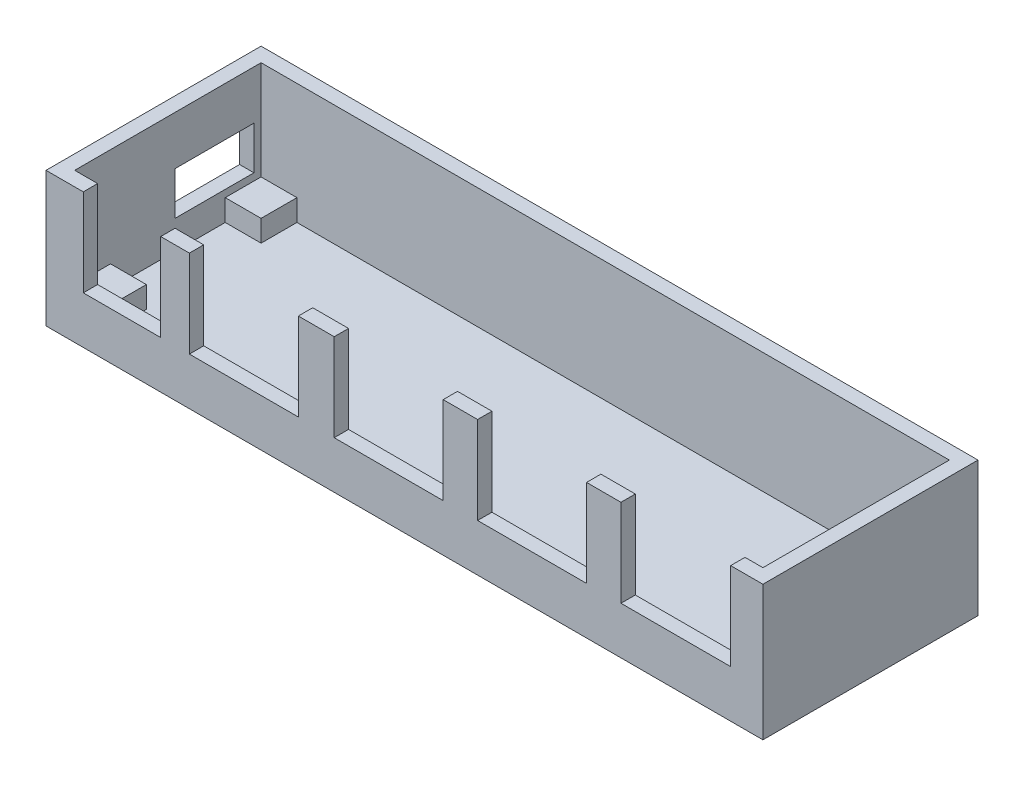
SolidWorks part; units mm, degrees
ref_plane "Front Plane" through (0, 0, 0) normal (0, 0, 1) x (1, 0, 0)
ref_plane "Top Plane" through (0, 0, 0) normal (0, 1, 0) x (1, 0, 0)
ref_plane "Right Plane" through (0, 0, 0) normal (1, 0, 0) x (0, 0, -1)
sketch "Sketch1" plane through (0, 0, 0) normal (0, 1, 0) x (1, 0, 0)
  line L0 (-87.4712, -27.9663) -> (8.5288, -27.9663)
  line L1 (-89.4712, -55.9663) -> (10.5288, -55.9663)
  line L2 (-89.4712, -55.9663) -> (-89.4712, -25.9663)
  line L3 (-89.4712, -25.9663) -> (10.5288, -25.9663)
  line L4 (10.5288, -55.9663) -> (10.5288, -25.9663)
  line L5 (8.5288, -53.9663) -> (8.5288, -27.9663)
  line L6 (-87.4712, -53.9663) -> (8.5288, -53.9663)
  line L7 (-87.4712, -53.9663) -> (-87.4712, -27.9663)
  line L8 (6.0288, -53.9663) -> (6.0288, -55.9663)
  line L9 (-9.2712, -53.9663) -> (-9.2712, -55.9663)
  line L10 (-14.0712, -53.9663) -> (-14.0712, -55.9663)
  line L11 (-34.0712, -53.9663) -> (-34.0712, -55.9663)
  line L12 (-54.2712, -53.9663) -> (-54.2712, -55.9663)
  line L13 (-29.2712, -53.9663) -> (-29.2712, -55.9663)
  line L14 (-49.2712, -53.9663) -> (-49.2712, -55.9663)
  line L15 (-69.4712, -53.9663) -> (-69.4712, -55.9663)
  line L16 (-73.4712, -53.9663) -> (-73.4712, -55.9663)
  line L17 (-84.2712, -53.9663) -> (-84.2712, -55.9663)
  line L18 (-39.9712, -12.3854) -> (-39.9712, -67.4293) construction
  line L20 (8.5288, -27.9663) -> (8.5288, -32.9663)
  line L24 (-87.4712, -27.9663) -> (-87.4712, -32.9663)
  line L25 (-91.4683, -40.9663) -> (18.0521, -40.9663) construction
  line L28 (-87.4712, -53.9663) -> (-87.4712, -48.9663)
  dimension "D1" = 2
  dimension "D2" = 2.5
  dimension "D3" = 17.8
  dimension "D6" = 15.2
  dimension "D7" = 3.2
  dimension "D8" = 47.5
  dimension "D9" = 14
  dimension "D5" = 18
  dimension "D4" = 5
  dimension "D10" = 4.8
  dimension "D11" = 37.8
  dimension "D12" = 4.8
  dimension "D13" = 15.2
extrude "Boss-Extrude1" add sketch "Sketch1" along normal blind 16.8 contours L17 L6 L7 L0 L5 L8 L1 L4 L3 L2 | L6 L16 L1 L15 | L14 L6 L12 L1 | L13 L6 L11 L1 | L6 L10 L1 L9 region at (-88.5153, 0, 30.4663) region at (-11.6712, 0, 54.9663) region at (-71.4712, 0, 54.9663) region at (-31.6712, 0, 54.9663) region at (-51.7712, 0, 54.9663)
ref_plane "Plane1" [suppressed] through (-87.4712, 0, 27.9663) normal (1, 0, 0) x (0, 0, -1)
extrude "Boss-Extrude2" add sketch "Sketch1<3>" against normal blind 2 contours L1 L4 L3 L2
sketch "Sketch1<3>" plane through (0, 0, 0) normal (0, 1, 0) x (1, 0, 0) same geometry as "Sketch1"
extrude "Boss-Extrude4" add sketch "Sketch1<6>" along normal blind 4.6 contours L6 L17 L1 L16 | L6 L15 L1 L12 | L6 L14 L1 L11 | L6 L13 L1 L10 | L6 L9 L1 L8 region at (-1.6212, 0, 54.9663) region at (-78.8712, 0, 54.9663) region at (-21.6712, 0, 54.9663) region at (-61.8712, 0, 54.9663) region at (-41.6712, 0, 54.9663)
sketch "Sketch1<6>" plane through (0, 0, 0) normal (0, 1, 0) x (1, 0, 0) same geometry as "Sketch1"
sketch "Sketch3" plane through (0, 0, 0) normal (0, 1, 0) x (1, 0, 0)
  line L0 (-39.4712, -55.9663) -> (-39.4712, -10.1821) construction
  line L1 (-87.4712, -27.9663) -> (-82.4712, -27.9663)
  line L2 (-87.4712, -27.9663) -> (-87.4712, -32.9663)
  line L3 (-87.4712, -32.9663) -> (-82.4712, -32.9663)
  line L4 (-82.4712, -27.9663) -> (-82.4712, -32.9663)
  line L5 (-49.2712, -55.9663) -> (-34.0712, -55.9663) construction
  line L6 (8.5288, -40.9663) -> (-94.4069, -40.9663) construction
  line L7 (8.5288, -53.9663) -> (8.5288, -27.9663) construction
  line L8 (8.5288, -27.9663) -> (8.5288, -32.9663)
  line L9 (8.5288, -27.9663) -> (3.5288, -27.9663)
  line L10 (3.5288, -27.9663) -> (3.5288, -32.9663)
  line L11 (8.5288, -32.9663) -> (3.5288, -32.9663)
  line L12 (8.5288, -48.9663) -> (3.5288, -48.9663)
  line L13 (3.5288, -53.9663) -> (3.5288, -48.9663)
  line L14 (8.5288, -53.9663) -> (3.5288, -53.9663)
  line L15 (8.5288, -53.9663) -> (8.5288, -48.9663)
  line L16 (-82.4712, -53.9663) -> (-82.4712, -48.9663)
  line L17 (-87.4712, -48.9663) -> (-82.4712, -48.9663)
  line L18 (-87.4712, -53.9663) -> (-87.4712, -48.9663)
  line L19 (-87.4712, -53.9663) -> (-82.4712, -53.9663)
extrude "Boss-Extrude5" add sketch "Sketch3" along normal blind 3
sketch "Sketch4" plane through (-89.4712, 0, 0) normal (-1, 0, 0) x (0, 0, 1)
  line L0 (28.9663, -2) -> (28.9663, 4)
  line L1 (55.9663, -2) -> (25.9663, -2) construction
  line L2 (25.9663, 16.8) -> (25.9663, -2) construction
  line L4 (28.9663, 4) -> (39.9663, 4)
  line L5 (28.9663, 4) -> (28.9663, 10)
  line L6 (28.9663, 10) -> (39.9663, 10)
  line L7 (39.9663, 4) -> (39.9663, 10)
  dimension "D1" = 3
extrude "Cut-Extrude2" cut sketch "Sketch4" against normal blind 4 contours L5 L6 L7 L4
